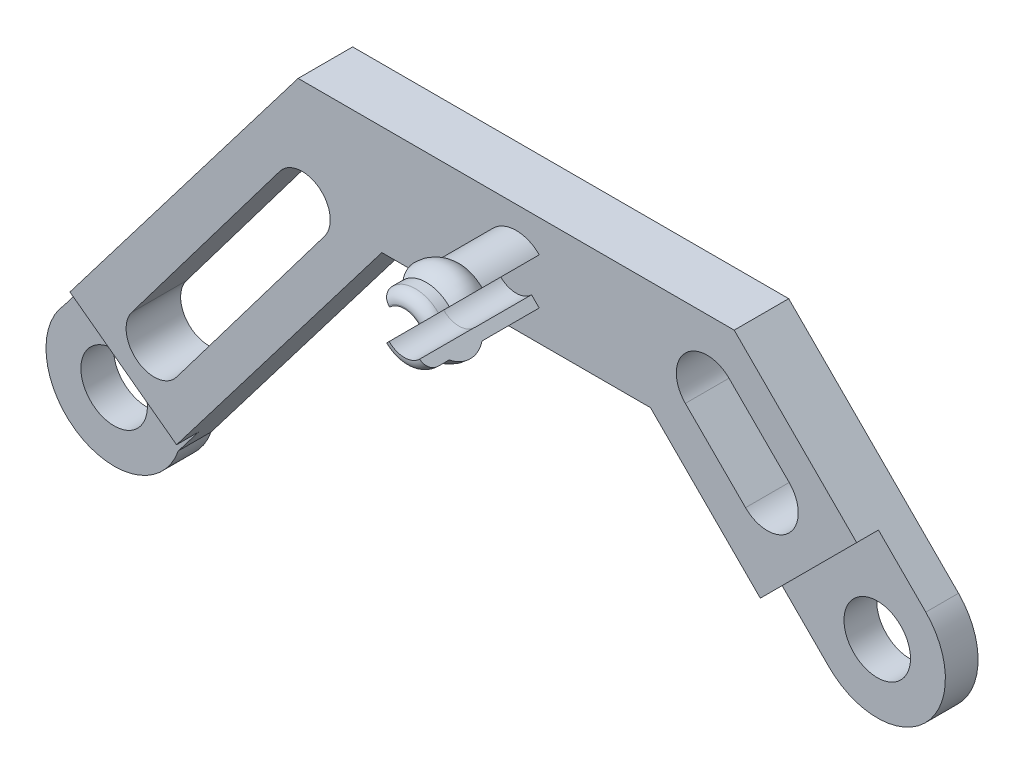
SolidWorks part; units mm, degrees
ref_plane "Płaszczyzna przednia" through (0, 0, 0) normal (0, 0, 1) x (1, 0, 0)
ref_plane "Płaszczyzna górna" through (0, 0, 0) normal (0, 1, 0) x (1, 0, 0)
ref_plane "Płaszczyzna prawa" through (0, 0, 0) normal (1, 0, 0) x (0, 0, -1)
sketch "Szkic1" plane through (0, 0, 0) normal (0, 0, 1) x (1, 0, 0)
  line L0 (-20, 0) -> (20, 0)
  line L1 (-12.3211, -10) -> (12.3211, -10)
  line L2 (-20, 0) -> (-43.4519, -30.7392)
  line L3 (-12.3211, -10) -> (-32.9894, -37.0907)
  line L4 (12.3211, -10) -> (26.6118, -24.3281)
  line L5 (20, 0) -> (35.5748, -15.6156)
  arc A0 (-43.4519, -30.7392) -> (-32.9894, -37.0907) centre (-38.8794, -35) ccw
  arc A1 (26.6118, -24.3281) -> (35.5748, -15.6156) centre (31.1206, -20) ccw
  circle A2 centre (-38.8794, -35) radius 3.05
  circle A3 centre (31.1206, -20) radius 3.05
  point P2 (0, 0)
  point P3 (0, -10)
  dimension "D6" = 6.25
  dimension "D7" = 6.1
  dimension "D8" = 6.1
  dimension "D1" = 40
  dimension "D2" = 10
  dimension "D3" = 10
  dimension "D4" = 70
  dimension "D5" = 35
extrude "Dodanie-wyciągnięcie1" add sketch "Szkic1" along normal blind 5
sketch "Szkic3" plane through (0, 0, 0) normal (0, 0, -1) x (-1, 0, 0)
  line L0 (19.6296, -9.7758) -> (33.2072, -27.7594) construction
  line L1 (21.683, -8.2254) -> (35.2607, -26.209)
  line L2 (17.5761, -11.3262) -> (31.1537, -29.3098)
  arc A0 (21.683, -8.2254) -> (17.5761, -11.3262) centre (19.6296, -9.7758) ccw
  arc A1 (31.1537, -29.3098) -> (35.2607, -26.209) centre (33.2072, -27.7594) ccw
  point P2 (26.4184, -18.7676)
extrude "Wytnij-wyciągnięcie2" cut sketch "Szkic3" against normal blind 10
sketch "Szkic4" plane through (0, 0, 0) normal (0, 0, -1) x (-1, 0, 0)
  line L0 (-17.5195, -6.0599) -> (-23.0418, -11.5822) construction
  line L1 (-15.5177, -8.0618) -> (-21.04, -13.5841)
  line L2 (-19.5214, -4.0581) -> (-25.0437, -9.5804)
  arc A0 (-15.5177, -8.0618) -> (-19.5214, -4.0581) centre (-17.5195, -6.0599) ccw
  arc A1 (-25.0437, -9.5804) -> (-21.04, -13.5841) centre (-23.0418, -11.5822) ccw
  point P2 (-20.2807, -8.8211)
extrude "Wytnij-wyciągnięcie4" cut sketch "Szkic4" against normal blind 10
sketch "Szkic5" plane through (0, 0, 5) normal (0, 0, 1) x (1, 0, 0)
  line L2 (-1.9225, -4.5282) -> (-2.8786, -4.2597)
  line L3 (-1.9255, -5.6091) -> (-2.8786, -5.8768)
  line L4 (1.9255, -4.5274) -> (2.8786, -4.2597)
  line L5 (1.9255, -5.6091) -> (2.8786, -5.8768)
  arc A2 (-2.8786, -4.2597) -> (2.8786, -4.2597) centre (0, -5.0682) cw
  arc A3 (-2.8786, -5.8768) -> (2.8786, -5.8768) centre (0, -5.0682) ccw
  arc A4 (-1.9255, -5.6091) -> (1.9255, -5.6091) centre (0, -5.0682) ccw
  arc A5 (-1.9225, -4.5282) -> (1.9255, -4.5274) centre (0.0016, -5.0764) cw
  point P1 (0.0016, -5.0764)
  point P6 (0, -5.0682)
  point P8 (0, -5.0682)
extrude "Dodanie-wyciągnięcie2" add sketch "Szkic5" along normal blind 5.25
sketch "Szkic6" plane through (0, 0, 0) normal (1, 0, 0) x (0, 0, -1)
  line L0 (-10.25, -2.0782) -> (-10.25, -3.169)
  line L2 (-10.25, -2.0782) -> (-10.25, -4.2597) construction
  line L3 (-10.25, -3.169) -> (-13.25, -3.169)
  line L5 (-13.25, -3.169) -> (-15.25, -3.169)
  line L6 (-15.25, -3.169) -> (-15.25, -2.0782)
  line L7 (-15.25, -2.0782) -> (-13.25, -2.0782)
  line L8 (-10.25, -5.0764) -> (-16.033, -5.0764) construction
  arc A0 (-13.25, -2.0782) -> (-10.25, -2.0782) centre (-11.75, -3.5782) cw
sketch3d "Szkic 3D1"
  line L0 (0.0016, -5.0764, 10.25) -> (0.0016, -5.0764, -3.8761) construction
  line L1 (0.0016, -5.0764, 10.25) -> (0.0016, -5.0764, 5) construction
revolve "Obrót1" add sketch "Szkic6" angle 45 about L8 other way angle 45
sketch "Szkic7" plane through (0, 0, 0) normal (1, 0, 0) x (0, 0, -1)
  line L0 (-10.25, -8.0582) -> (-10.25, -7.0582)
  line L2 (-10.25, -5.8768) -> (-10.25, -8.0582) construction
  line L3 (-10.25, -7.0582) -> (-13.25, -7.0582)
  line L5 (-13.25, -7.0582) -> (-15.25, -7.0582)
  line L6 (-15.25, -7.0582) -> (-15.25, -8.0582)
  line L7 (-15.25, -8.0582) -> (-13.25, -8.0582)
  line L8 (-10.25, -5.0764) -> (-16.0253, -5.0764) construction
  arc A0 (-13.25, -8.0582) -> (-10.25, -8.0582) centre (-11.75, -6.5582) ccw
revolve "Obrót2" add sketch "Szkic7" angle 45 about L8 other way angle 45
sketch3d "Szkic 3D2" plane through (0, 0, 0) normal (0, 0, 1) x (1, 0, 0)
  dimension "D1" = 5
sketch "Szkic8" plane through (0, 0, 5) normal (0, 0, 1) x (1, 0, 0)
  line L0 (32.4189, -10.076) -> (21.2648, -21.2301)
  line L1 (21.2648, -21.2301) -> (33.2671, -33.2324)
  line L2 (33.2671, -33.2324) -> (44.4212, -22.0783)
  line L3 (44.4212, -22.0783) -> (32.4189, -10.076)
  line L4 (-43.1055, -25.8261) -> (-28.0781, -36.9575)
  line L5 (-28.0781, -36.9575) -> (-36.7261, -48.6324)
  line L6 (-36.7261, -48.6324) -> (-51.7536, -37.501)
  line L7 (-51.7536, -37.501) -> (-43.1055, -25.8261)
extrude "Wytnij-wyciągnięcie5" cut sketch "Szkic8" against normal blind 2
sketch "Szkic9" plane through (0, 0, 10.25) normal (0, 0, 1) x (1, 0, 0)
  line L0 (-2.5594, -2.517) -> (-1.3488, -3.7276)
  line L1 (-2.1201, -2.9564) -> (-1.3488, -3.7276) construction
  line L2 (-1.3488, -3.7276) -> (1.3488, -3.7276)
  line L3 (1.3488, -3.7276) -> (2.5594, -2.517)
  line L4 (2.5594, -2.517) -> (3.6532, -6.0321)
  line L5 (3.6532, -6.0321) -> (2.5478, -7.6242)
  line L6 (2.5478, -7.6242) -> (1.4013, -6.4778)
  line L7 (1.4013, -6.4778) -> (-1.4013, -6.4778)
  line L8 (-1.4013, -6.4778) -> (-2.5478, -7.6242)
  line L9 (-2.5478, -7.6242) -> (-3.5651, -4.9629)
  line L10 (-3.5651, -4.9629) -> (-2.5594, -2.517)
extrude "Wytnij-wyciągnięcie6" cut sketch "Szkic9" against normal up to surface (5.25 mm away) up to face at (-2.307, -14.1849, 5)
fillet "Zaokrąglenie1" radius 1 2 edges at (0, -8.0582, 15.25) (0, -2.0782, 15.25)
